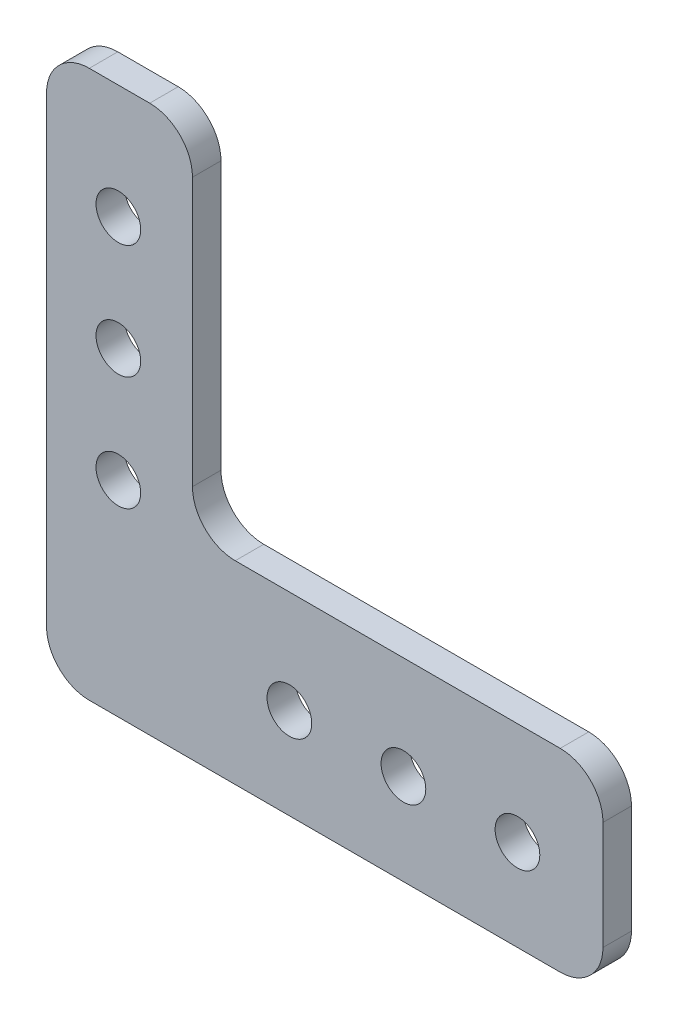
SolidWorks part; units mm, degrees
material "6061-T6 (SS)"
ref_plane "Front Plane" through (0, 0, 0) normal (0, 0, 1) x (1, 0, 0)
ref_plane "Top Plane" through (0, 0, 0) normal (0, 1, 0) x (1, 0, 0)
ref_plane "Right Plane" through (0, 0, 0) normal (1, 0, 0) x (0, 0, -1)
sketch "Sketch1" plane through (0, 0, 0) normal (0, 0, 1) x (1, 0, 0)
  line L1 (-34.925, -31.75) -> (34.925, -31.75)
  line L2 (-34.925, -31.75) -> (-34.925, 31.75)
  line L3 (-34.925, 31.75) -> (34.925, 31.75)
  line L4 (34.925, -31.75) -> (34.925, 31.75)
  line L5 (-34.925, -31.75) -> (34.925, 31.75) construction
  line L6 (-34.925, 31.75) -> (34.925, -31.75) construction
  line L7 (34.925, 31.75) -> (-10.795, 31.75)
  line L8 (34.925, 31.75) -> (34.925, -7.62)
  line L9 (34.925, -7.62) -> (-10.795, -7.62)
  line L10 (-10.795, 31.75) -> (-10.795, -7.62)
  line L11 (-34.925, -31.75) -> (-27.051, -31.75)
  line L12 (-34.925, -31.75) -> (-34.925, 31.75)
  line L13 (-34.925, 31.75) -> (-27.051, 31.75)
  line L14 (-27.051, -31.75) -> (-27.051, 31.75)
  line L15 (-27.051, -31.75) -> (34.925, -31.75)
  line L16 (-27.051, -31.75) -> (-27.051, -29.21)
  line L17 (-27.051, -29.21) -> (34.925, -29.21)
  line L18 (34.925, -31.75) -> (34.925, -29.21)
  circle A0 centre (-19.05, -19.05) radius 2.4892
  circle A1 centre (-19.05, -6.35) radius 2.4892
  circle A2 centre (-19.05, 6.35) radius 2.4892
  circle A3 centre (-19.05, 19.05) radius 2.4892
  circle A4 centre (0, -19.05) radius 2.4892
  circle A5 centre (12.7, -19.05) radius 2.4892
  circle A6 centre (25.4, -19.05) radius 2.4892
  point P0 (0, 0)
  dimension "D7" = 4.9784
  dimension "D1" = 69.85
  dimension "D2" = 63.5
  dimension "D3" = 24.13
  dimension "D4" = 24.13
  dimension "D5" = 7.874
  dimension "D6" = 63.5
  dimension "D8" = 15.875
  dimension "D9" = 12.7
  dimension "D10" = 12.7
  dimension "D11" = 12.7
  dimension "D12" = 12.7
  dimension "D13" = 12.7
  dimension "D14" = 27.051
  dimension "D15" = 12.7
  dimension "D16" = 2.54
extrude "Boss-Extrude1" add sketch "Sketch1" along normal blind 3.175 contours L14 L17 L4 L9 L10 L3 A6 A5 A4 A3 A2 A1 A0 | A0 region at (-3.3126, -8.582, 0) region at (-19.05, -19.05, 0)
fillet "Fillet1" radius 4.7625 6 edges at (-27.051, 31.75, 1.5875) (-10.795, 31.75, 1.5875) (-10.795, -7.62, 1.5875) (34.925, -7.62, 1.5875) (34.925, -29.21, 1.5875) (-27.051, -29.21, 1.5875)
